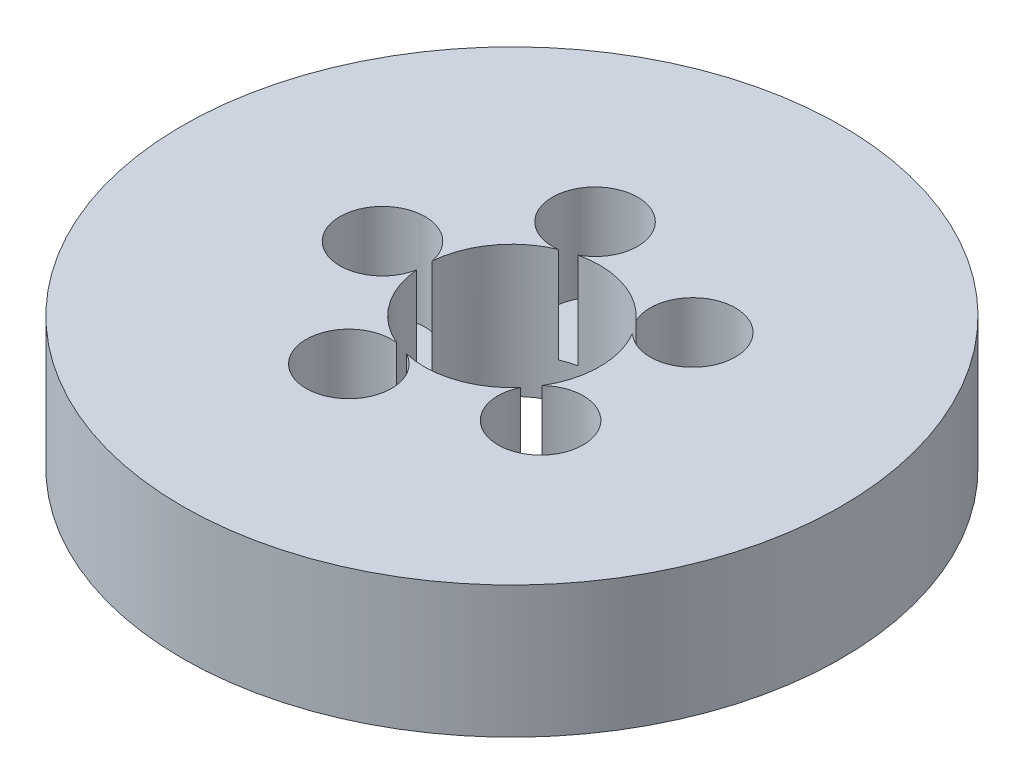
SolidWorks part; units mm, degrees
ref_plane "Front Plane" through (0, 0, 0) normal (0, 0, 1) x (1, 0, 0)
ref_plane "Top Plane" through (0, 0, 0) normal (0, 1, 0) x (1, 0, 0)
ref_plane "Right Plane" through (0, 0, 0) normal (1, 0, 0) x (0, 0, -1)
sketch "Sketch1" plane through (0, 0, 0) normal (0, 1, 0) x (1, 0, 0)
  circle A0 centre (0, 0) radius 75
  dimension "FLANGE_OD" = 150
extrude "Boss-Extrude1" add sketch "Sketch1" along normal blind 30
sketch "Sketch2" plane through (0, 0, 0) normal (0, 1, 0) x (1, 0, 0)
  circle A0 centre (0, 0) radius 20
  dimension "BORE_D" = 40
extrude "Cut-Extrude1" cut sketch "Sketch2" along normal through all
sketch "Sketch3" plane through (0, 30, 0) normal (0, 1, 0) x (1, 0, 0)
  circle A0 centre (0, 0) radius 29.4608 construction
  circle A1 centre (-29.4608, 0) radius 9.7047
  dimension "BOLT_D" = 19.4093
  dimension "BOLT_PCD" = 58.9216
extrude "Cut-Extrude2" cut sketch "Sketch3" against normal blind 21.7902
pattern_circular "CirPattern1" count 5 over 360 about axis through (0, 0, 0) along (0, 1, 0) of "Cut-Extrude2"
